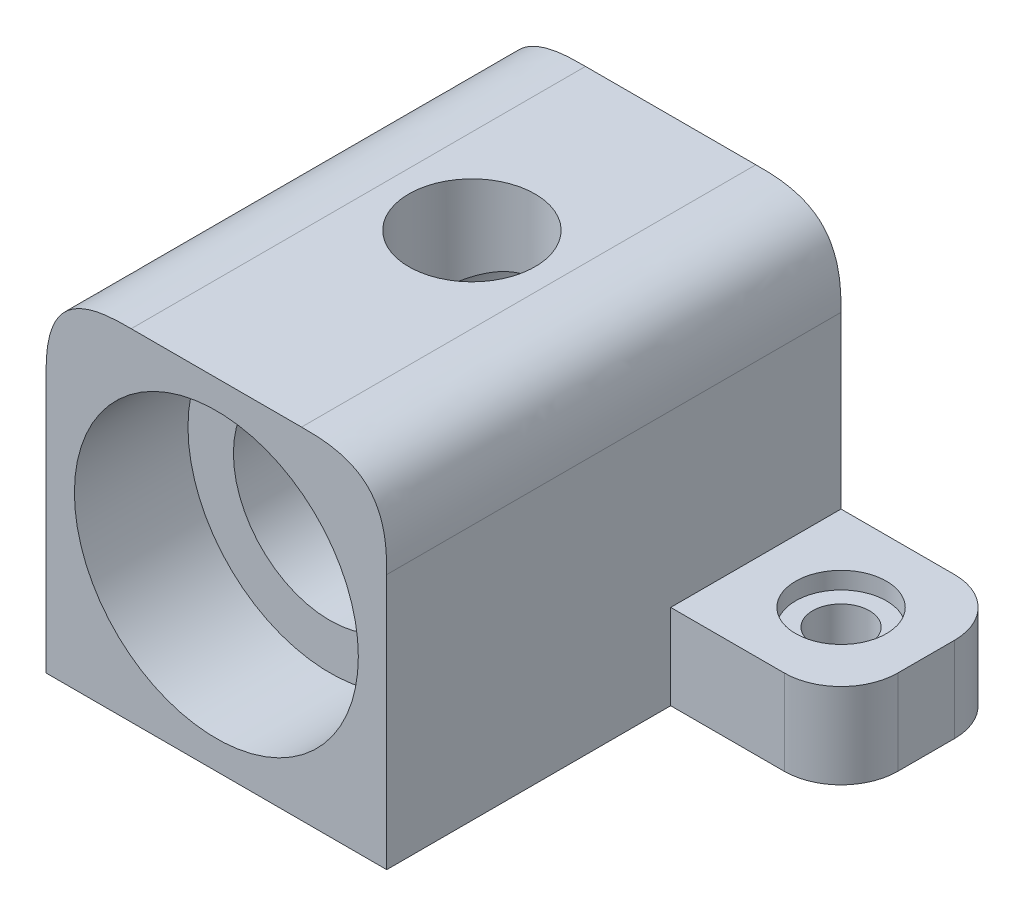
SolidWorks part; units mm, degrees
ref_plane "Front Plane" through (0, 0, 0) normal (0, 0, 1) x (1, 0, 0)
ref_plane "Top Plane" through (0, 0, 0) normal (0, 1, 0) x (1, 0, 0)
ref_plane "Right Plane" through (0, 0, 0) normal (1, 0, 0) x (0, 0, -1)
sketch "Sketch1" plane through (0, 0, 0) normal (0, 0, 1) x (1, 0, 0)
  line L1 (15, -15) -> (-15, -15)
  line L2 (15, -15) -> (15, 15)
  line L3 (15, 15) -> (-15, 15)
  line L4 (-15, -15) -> (-15, 15)
  line L5 (15, -15) -> (-15, 15) construction
  line L6 (15, 15) -> (-15, -15) construction
  point P0 (0, 0)
  dimension "D1" = 30
  dimension "D2" = 30
extrude "Boss-Extrude1" add sketch "Sketch1" along normal blind 35 and the other way blind 5
fillet "Fillet1" radius 7.5 2 edges at (-15, 15, 15) (15, 15, 15) curvature continuous yes
sketch "Sketch2" plane through (0, 0, 0) normal (0, 0, 1) x (1, 0, 0)
  circle A0 centre (0, 0) radius 8.5
  dimension "D1" = 17
extrude "Cut-Extrude1" cut sketch "Sketch2" along normal blind 60
sketch "Sketch3" plane through (15, 0, 0) normal (1, 0, 0) x (0, 0, -1)
  line L1 (5, -15) -> (-10, -15)
  line L2 (5, -15) -> (5, -7.5)
  line L3 (5, -7.5) -> (-10, -7.5)
  line L4 (-10, -15) -> (-10, -7.5)
  dimension "D1" = 7.5
  dimension "D2" = 15
extrude "Boss-Extrude2" add sketch "Sketch3" along normal blind 15
sketch "Sketch5" plane through (-15, 0, 0) normal (-1, 0, 0) x (0, 0, 1)
  line L1 (-5, -15) -> (10, -15)
  line L2 (-5, -15) -> (-5, -7.5)
  line L3 (-5, -7.5) -> (10, -7.5)
  line L4 (10, -15) -> (10, -7.5)
  dimension "D1" = 15
  dimension "D2" = 7.5
extrude "Boss-Extrude4" add sketch "Sketch5" along normal blind 15
sketch "Sketch11" plane through (0, 0, 35) normal (0, 0, 1) x (1, 0, 0)
  circle A0 centre (0, 0) radius 12.5
  dimension "D1" = 25
extrude "Cut-Extrude3" cut sketch "Sketch11" against normal blind 10
fillet "Fillet8" radius 5 4 edges at (30, -11.25, 10) (30, -11.25, -5) (-30, -11.25, 10) (-30, -11.25, -5)
sketch "Sketch15" plane through (0, -7.5, 0) normal (0, 1, 0) x (1, 0, 0)
  line L0 (30, 0) -> (30, -5) construction
  line L1 (-30, -5) -> (-30, 0) construction
  line L2 (25, -10) -> (15, -10) construction
  line L3 (-25, 5) -> (-15, 5) construction
  circle A0 centre (22.5, -2.5) radius 4
  circle A1 centre (-22.5, -2.5) radius 4
  point P8 (0, 0)
  dimension "D2" = 8
  dimension "D3" = 8
  dimension "D1" = 7.5
  dimension "D4" = 7.5
  dimension "D5" = 7.5
  dimension "D6" = 7.5
extrude "Cut-Extrude5" cut sketch "Sketch15" against normal blind 1.5
sketch "Sketch19" plane through (0, 15, 0) normal (0, 1, 0) x (1, 0, 0)
  line L0 (7.5, 5) -> (-7.5, 5) construction
  circle A0 centre (0, -12.5) radius 5.5563
  point P2 (0, 0)
  dimension "D1" = 11.1125
  dimension "D2" = 17.5
extrude "Cut-Extrude10" cut sketch "Sketch19" against normal blind 11.5
sketch "Sketch21" plane through (0, -9, 0) normal (0, 1, 0) x (1, 0, 0)
  circle A0 centre (-22.5, -2.5) radius 2.5
  circle A1 centre (22.5, -2.5) radius 2.5
  dimension "D1" = 5
  dimension "D2" = 5
extrude "Cut-Extrude11" cut sketch "Sketch21" against normal blind 11.5
equation "\"7.5.000000mm\"=5"
